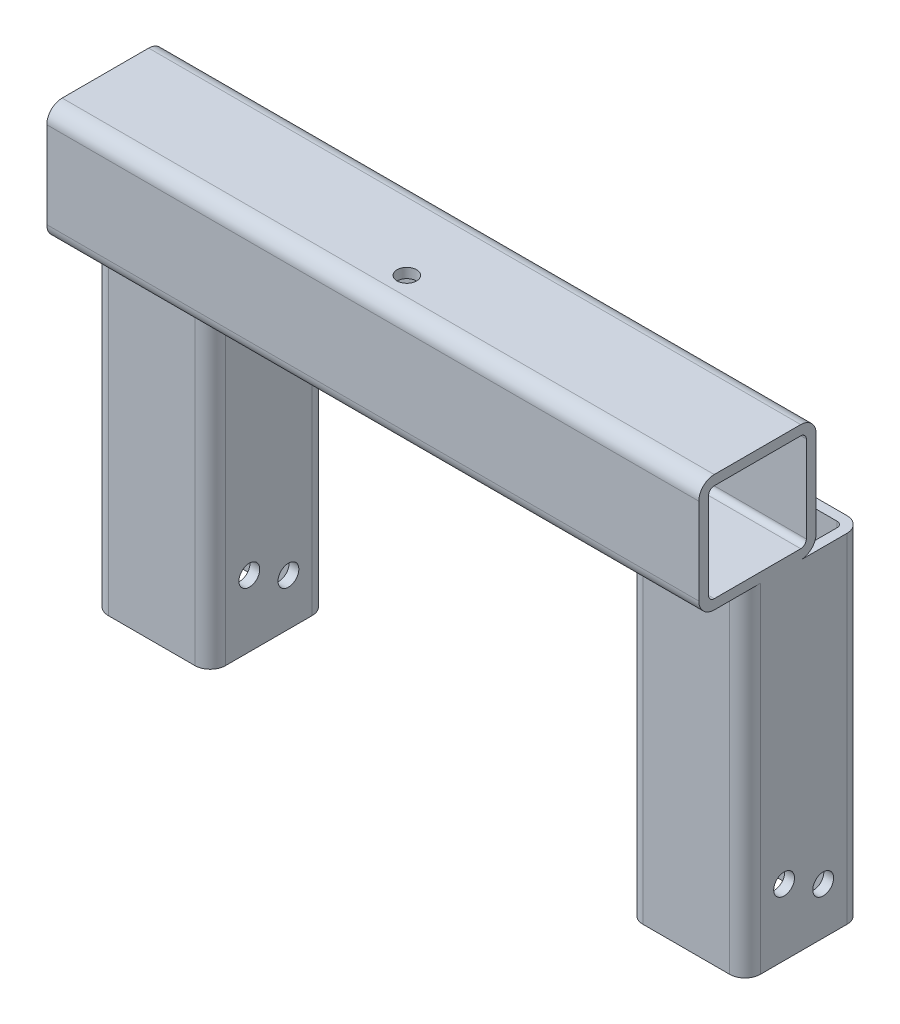
SolidWorks part; units mm, degrees
ref_plane "Front Plane" through (0, 0, 0) normal (0, 0, 1) x (1, 0, 0)
ref_plane "Top Plane" through (0, 0, 0) normal (0, 1, 0) x (1, 0, 0)
ref_plane "Right Plane" through (0, 0, 0) normal (1, 0, 0) x (0, 0, -1)
sketch "Sketch1" plane through (0, 0, 0) normal (0, 1, 0) x (1, 0, 0)
  line L0 (-14.05, 19.05) -> (14.05, 19.05)
  line L1 (19.05, 14.05) -> (19.05, -14.05)
  line L2 (-15.875, 14.05) -> (-15.875, -14.05)
  line L3 (-14.05, -15.875) -> (14.05, -15.875)
  line L4 (14.05, -19.05) -> (-14.05, -19.05)
  line L5 (-19.05, -14.05) -> (-19.05, 14.05)
  line L6 (0, 19.05) -> (0, -19.05) construction
  line L7 (-19.05, 0) -> (19.05, 0) construction
  line L8 (15.875, -14.05) -> (15.875, 14.05)
  line L9 (14.05, 15.875) -> (-14.05, 15.875)
  line L10 (0, 15.875) -> (0, -15.875) construction
  line L11 (-15.875, 0) -> (15.875, 0) construction
  arc A0 (14.05, 19.05) -> (19.05, 14.05) centre (14.05, 14.05) cw
  arc A1 (19.05, -14.05) -> (14.05, -19.05) centre (14.05, -14.05) cw
  arc A2 (-14.05, -19.05) -> (-19.05, -14.05) centre (-14.05, -14.05) cw
  arc A3 (-19.05, 14.05) -> (-14.05, 19.05) centre (-14.05, 14.05) cw
  arc A4 (-15.875, -14.05) -> (-14.05, -15.875) centre (-14.05, -14.05) ccw
  arc A5 (14.05, -15.875) -> (15.875, -14.05) centre (14.05, -14.05) ccw
  arc A6 (15.875, 14.05) -> (14.05, 15.875) centre (14.05, 14.05) ccw
  arc A7 (-14.05, 15.875) -> (-15.875, 14.05) centre (-14.05, 14.05) ccw
  point P33 (0, 0)
  dimension "D1" = 5
  dimension "D2" = 3.175
  dimension "D3" = 38.1
extrude "Boss-Extrude1" add sketch "Sketch1" along normal blind 110
ref_plane "Plane1" through (86.85, 0, 0) normal (1, 0, 0) x (0, 0, -1)
mirror "Mirror2" about plane through (86.85, 0, 0) normal (1, 0, 0) of bodies 101
sketch "Sketch2" plane through (86.85, 0, 0) normal (1, 0, 0) x (0, 0, -1)
  line L0 (-29.05, 148.1) -> (-0.95, 148.1)
  line L1 (4.05, 143.1) -> (4.05, 115)
  line L2 (-30.875, 143.1) -> (-30.875, 115)
  line L3 (-29.05, 113.175) -> (-0.95, 113.175)
  line L4 (-0.95, 110) -> (-29.05, 110)
  line L5 (-34.05, 115) -> (-34.05, 143.1)
  line L6 (-15, 148.1) -> (-15, 110) construction
  line L7 (-34.05, 129.05) -> (4.05, 129.05) construction
  line L8 (0.875, 115) -> (0.875, 143.1)
  line L9 (-0.95, 144.925) -> (-29.05, 144.925)
  line L10 (-15, 144.925) -> (-15, 113.175) construction
  line L11 (-30.875, 129.05) -> (0.875, 129.05) construction
  line L12 (0, 0) -> (0, -17.0016) construction
  line L13 (14.05, 110) -> (-14.05, 110) construction
  arc A0 (-0.95, 148.1) -> (4.05, 143.1) centre (-0.95, 143.1) cw
  arc A1 (4.05, 115) -> (-0.95, 110) centre (-0.95, 115) cw
  arc A2 (-29.05, 110) -> (-34.05, 115) centre (-29.05, 115) cw
  arc A3 (-34.05, 143.1) -> (-29.05, 148.1) centre (-29.05, 143.1) cw
  arc A4 (-30.875, 115) -> (-29.05, 113.175) centre (-29.05, 115) ccw
  arc A5 (-0.95, 113.175) -> (0.875, 115) centre (-0.95, 115) ccw
  arc A6 (0.875, 143.1) -> (-0.95, 144.925) centre (-0.95, 143.1) ccw
  arc A7 (-29.05, 144.925) -> (-30.875, 143.1) centre (-29.05, 143.1) ccw
  dimension "D1" = 5
  dimension "D2" = 3.175
  dimension "D3" = 38.1
  dimension "D4" = 15
extrude "Boss-Extrude2" add sketch "Sketch2" along normal up to surface (105.9 mm away) and the other way up to surface (105.9 mm away) up to face at (192.75, 55, 0) other way up to face at (-19.05, 55, 0)
sketch "Sketch3" plane through (0, 110, 0) normal (0, -1, 0) x (1, 0, 0)
  circle A2 centre (86.8, 22.9375) radius 3.175
extrude "Cut-Extrude1" cut sketch "Sketch3" against normal up to surface (38.1 mm away) up to face at (86.85, 148.1, 15)
hole_wizard "1/4 Clearance Hole1" positions "Sketch4" profile "Sketch5" hole size "1/4" standard "ANSI Inch" end condition through all
sketch "Sketch4" plane through (-19.05, 0, 0) normal (-1, 0, 0) x (0, 0, 1)
  line L0 (-14.05, 0) -> (14.05, 0) construction
  point P0 (-6.35, 15.24)
  point P2 (6.35, 21.59)
  dimension "D1" = 15.24
  dimension "D2" = 12.7
  dimension "D3" = 6.35
  dimension "D4" = 6.35
sketch "Sketch5" plane through (-19.05, 15.24, -6.35) normal (0, 1, 0) x (0, 0, 1)
  line L0 (0, 0) -> (0, 211.8)
  line L1 (0, 211.8) -> (3.3782, 211.8)
  line L2 (3.3782, 211.8) -> (3.3782, 0)
  line L5 (3.3782, 0) -> (0, 0)
  line L11 (0, -6.35) -> (0, 107.95) construction
  dimension "Thru Hole Dia." = 6.7564
  dimension "Thru Hole Depth" = 211.8
